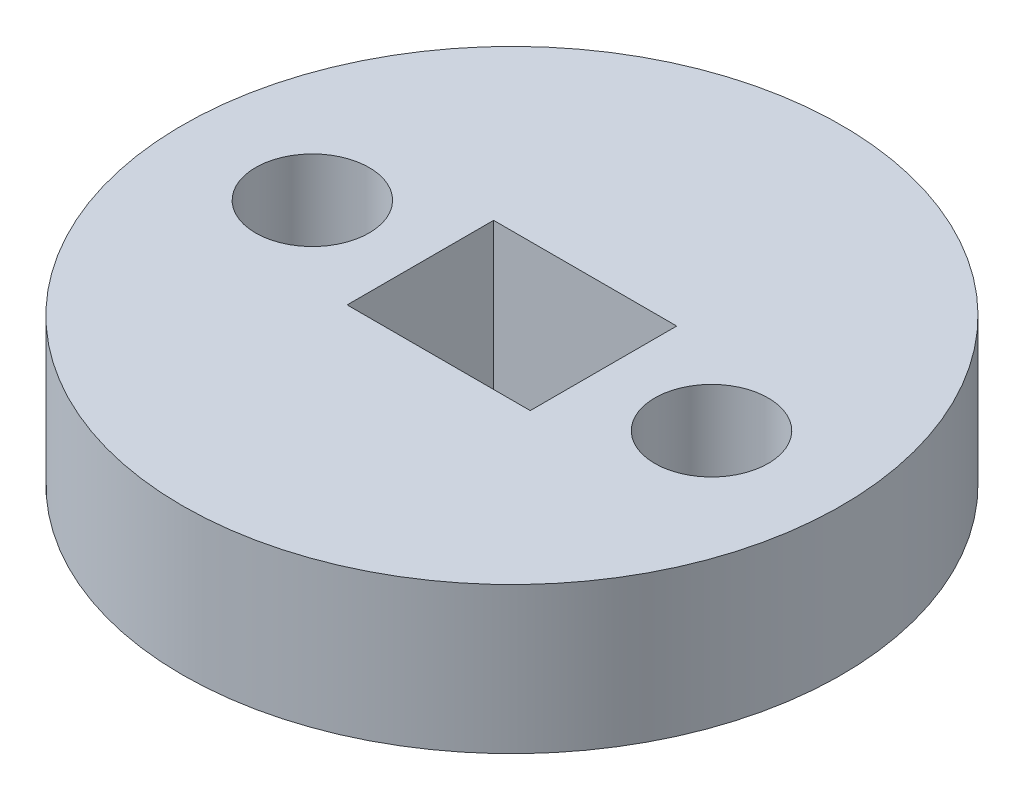
SolidWorks part; units mm, degrees
ref_plane "Front Plane" through (0, 0, 0) normal (0, 0, 1) x (1, 0, 0)
ref_plane "Top Plane" through (0, 0, 0) normal (0, 1, 0) x (1, 0, 0)
ref_plane "Right Plane" through (0, 0, 0) normal (1, 0, 0) x (0, 0, -1)
sketch "Sketch1" plane through (0, 0, 0) normal (0, 1, 0) x (1, 0, 0)
  circle A0 centre (0, 0) radius 9
  dimension "D1" = 18
base flange "Base-Flange1" sketch "Sketch1" thickness 4 reverse thickness direction no parameters "D1"=2
sketch "Sketch6" plane through (0, 0, 0) normal (0, 1, 0) x (1, 0, 0)
  line L1 (-2, 1.5) -> (2, 1.5)
  line L3 (0, -1.5) -> (2, -1.5)
  line L4 (0, -1.5) -> (-2, -1.5)
  arc A0 (-2, 1.5) -> (-2, -1.5) centre (0, 0) ccw
  arc A1 (2, -1.5) -> (2, 1.5) centre (0, 0) ccw
  point P7 (0, 1.5)
  dimension "D1" = 5
  dimension "D2" = 4
  dimension "D3" = 4
  dimension "D4" = 3
extrude "Cut-Extrude1" [suppressed] cut sketch "Sketch6" against normal blind 10
sketch "Sketch7" plane through (0, 0, 0) normal (0, 1, 0) x (1, 0, 0)
  line L0 (-5.45, 0) -> (5.45, 0) construction
  line L1 (-7, 0) -> (-9, 0) construction
  line L2 (7, 0) -> (9, 0) construction
  circle A0 centre (-5.45, 0) radius 1.55
  circle A1 centre (5.45, 0) radius 1.55
  circle A3 centre (0, 0) radius 9 construction
  point P4 (0, 0)
  dimension "D1" = 3.1
  dimension "D2" = 2
extrude "Cut-Extrude2" cut sketch "Sketch7" against normal blind 10 normal cut yes
sketch "Sketch8" plane through (0, 0, 0) normal (0, 1, 0) x (1, 0, 0)
  line L0 (0, 2) -> (0, -2) construction
  line L1 (-2.5, -2) -> (2.5, -2)
  line L2 (-2.5, -2) -> (-2.5, 2)
  line L3 (-2.5, 2) -> (2.5, 2)
  line L4 (2.5, -2) -> (2.5, 2)
  point P4 (0, 0)
  dimension "D1" = 5
  dimension "D2" = 4
extrude "Cut-Extrude3" cut sketch "Sketch8" against normal blind 10 normal cut yes
sketch "Bend-Lines1" [suppressed] plane through (0, 0, 0) normal (0, 1, 0) x (1, 0, 0)
sketch "Bounding-Box1" [suppressed] plane through (0, 0, 0) normal (0, 1, 0) x (1, 0, 0)
sheet metal parameters "Sheet-Metal1" thickness 4 parameters "D1"=2
flat pattern "Flat-Pattern1" [suppressed]
sketch "Bend-Lines2" plane through (0, 0, 0) normal (0, 1, 0) x (1, 0, 0)
sketch "Bounding-Box2" [suppressed] plane through (0, 0, 0) normal (0, 1, 0) x (1, 0, 0)
sheet metal parameters "Sheet-Metal2" thickness 4 parameters "D1"=2
flat pattern "Flat-Pattern1"
sketch "Bend-Lines2" plane through (0, 0, 0) normal (0, 1, 0) x (1, 0, 0)
sketch "Bounding-Box2" [suppressed] plane through (0, 0, 0) normal (0, 1, 0) x (1, 0, 0)
sheet metal parameters "Sheet-Metal3" thickness 4 parameters "D1"=2
flat pattern "Flat-Pattern1"
sketch "Bend-Lines2" plane through (0, 0, 0) normal (0, 1, 0) x (1, 0, 0)
sketch "Bounding-Box2" [suppressed] plane through (0, 0, 0) normal (0, 1, 0) x (1, 0, 0)
sheet metal parameters "Sheet-Metal4" thickness 4 parameters "D1"=2
flat pattern "Flat-Pattern1"
sketch "Bend-Lines2" plane through (0, 0, 0) normal (0, 1, 0) x (1, 0, 0)
sketch3d "Bounding-Box2" [suppressed]
  line L0 (-9.0385, 8.9612, 0) -> (-8.9611, -9.0386, 0) construction
  line L1 (8.9612, 9.0386, 0) -> (9.0386, -8.9611, 0) construction
  line L2 (-9.0385, 8.9612, 0) -> (8.9612, 9.0386, 0) construction
  line L3 (-8.9611, -9.0386, 0) -> (9.0386, -8.9611, 0) construction
